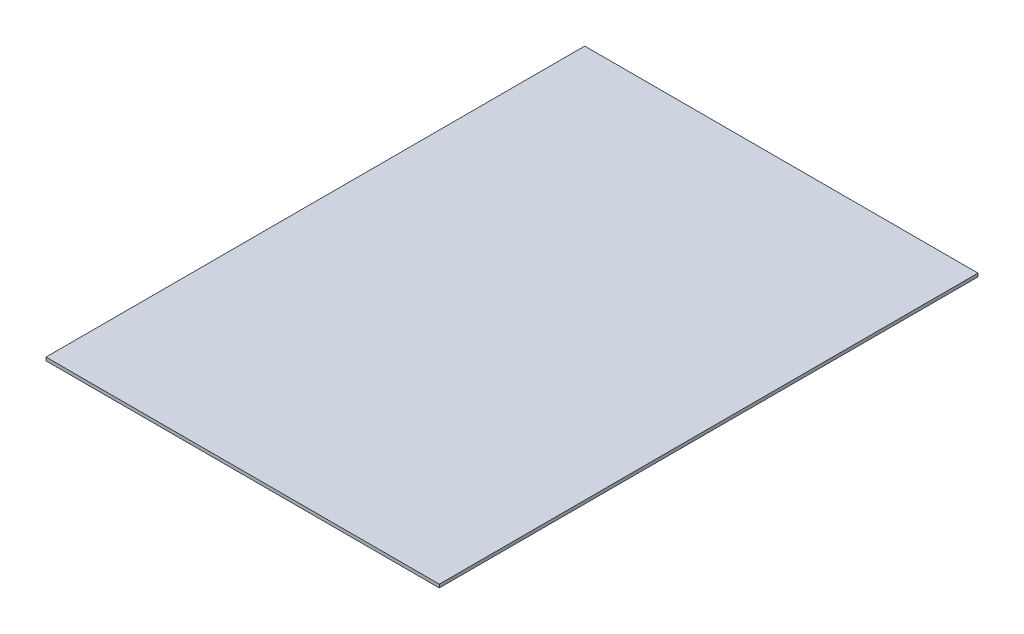
SolidWorks part; units mm, degrees
ref_plane "Front Plane" through (0, 0, 0) normal (0, 0, 1) x (1, 0, 0)
ref_plane "Top Plane" through (0, 0, 0) normal (0, 1, 0) x (1, 0, 0)
ref_plane "Right Plane" through (0, 0, 0) normal (1, 0, 0) x (0, 0, -1)
sketch "Sketch1" plane through (0, 0, 0) normal (0, 1, 0) x (1, 0, 0)
  line L1 (-30, 41.09) -> (30, 41.09)
  line L2 (-30, 41.09) -> (-30, -41.09)
  line L3 (-30, -41.09) -> (30, -41.09)
  line L4 (30, 41.09) -> (30, -41.09)
  point P4 (0, -41.09)
  point P6 (-30, 0)
  dimension "D1" = 60
  dimension "D2" = 82.18
extrude "Boss-Extrude1" add sketch "Sketch1" along normal blind 0.5
